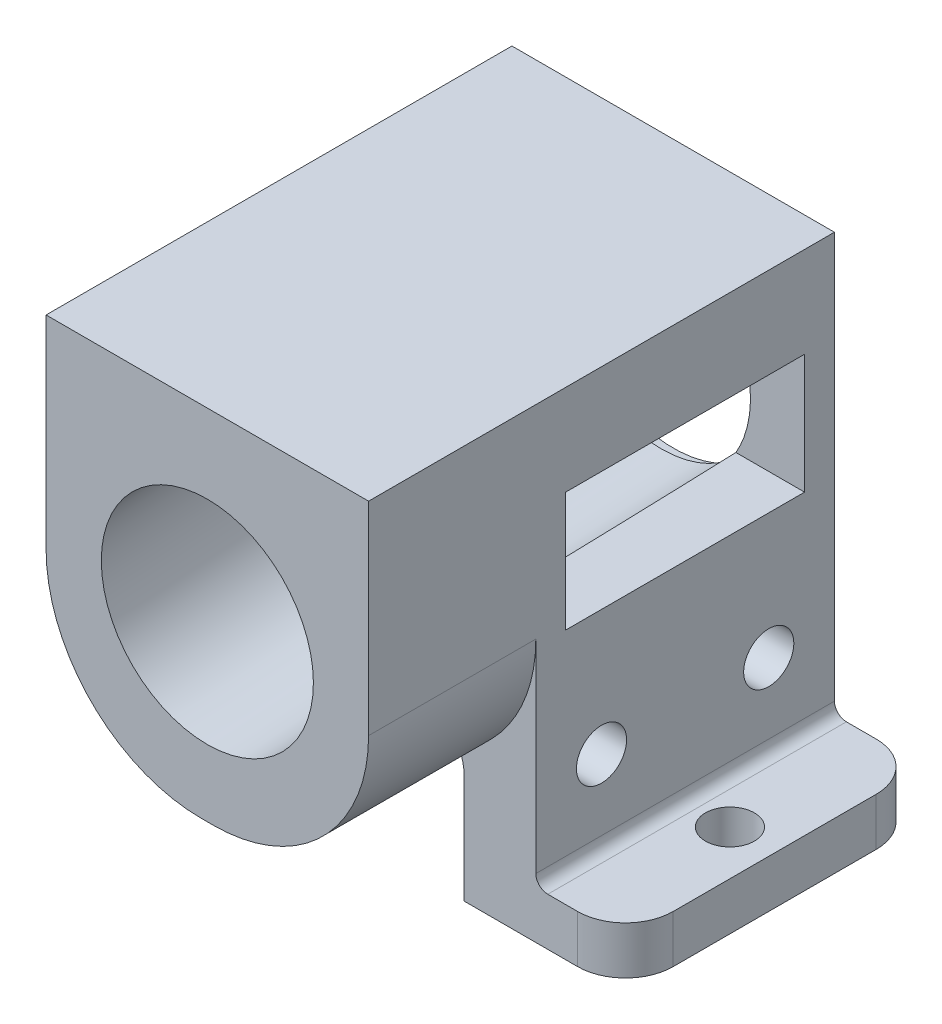
SolidWorks part; units mm, degrees
material "聚脂树脂"
ref_plane "前视基准面" through (0, 0, 0) normal (0, 0, 1) x (1, 0, 0)
ref_plane "上视基准面" through (0, 0, 0) normal (0, 1, 0) x (1, 0, 0)
ref_plane "右视基准面" through (0, 0, 0) normal (1, 0, 0) x (0, 0, -1)
sketch "草图1" plane through (0, 0, 0) normal (0, 0, 1) x (1, 0, 0)
  line L0 (0, 0) -> (0, 26.1)
  line L1 (-13.5, 39.6) -> (-13.5, 0)
  line L2 (-13.5, 39.6) -> (13.5, 39.6)
  line L3 (-13.5, 0) -> (13.5, 0)
  line L4 (13.5, 39.6) -> (13.5, 0)
  line L5 (-13.5, 39.6) -> (13.5, 0) construction
  line L6 (-13.5, 0) -> (13.5, 39.6) construction
  line L7 (13.5, 4) -> (-13.5, 4) construction
  line L8 (0, 4) -> (0, 0) construction
  line L9 (-13.5, 13.2062) -> (13.5, 13.2062)
  line L10 (-21, 4) -> (21, 4)
  line L11 (-21, 4) -> (-21, 0)
  line L12 (-21, 0) -> (21, 0)
  line L13 (21, 4) -> (21, 0)
  line L14 (-21, 4) -> (21, 0) construction
  line L15 (-21, 0) -> (21, 4) construction
  line L16 (-4, 13.2062) -> (4, 13.2062)
  line L17 (-4, 13.2062) -> (-4, 0)
  line L18 (-4, 0) -> (4, 0)
  line L19 (4, 13.2062) -> (4, 0)
  line L20 (-4, 13.2062) -> (4, 0) construction
  line L21 (-4, 0) -> (4, 13.2062) construction
  circle A0 centre (0, 26.1) radius 9
  circle A1 centre (0, 26.1) radius 13.5
  point P5 (0, 39.6)
  point P6 (0, 19.8)
  point P10 (0, 2)
  point P19 (0, 6.6031)
  point P26 (-4, 13.2062)
  dimension "D2" = 18
  dimension "D3" = 27
  dimension "D1" = 26.1
  dimension "D4" = 13.5
  dimension "D5" = 27
  dimension "D6" = 4
  dimension "0" = 0
  dimension "D7" = 4
  dimension "D8" = 42
  dimension "D9" = 8
  dimension "D10" = 13.5
extrude "凸台-拉伸3" add sketch "草图1" along normal blind 25 contours L0 A1 L9 | L9 A1 L0 | A1 L0 L10 L19 | A1 L17 L10 L0 | A1 L9 L4 | A1 L4 L2 | A1 L9 A0 | A1 L2 L1 | A1 L1 L9 | L11 L12 L1 L10 | L17 L10 L1 L3 | L19 L10 L0 L3 | L10 L17 L12 L0 | L13 L10 L4 L12 | L10 L19 L12 L4 region at (-2, 2, 0) region at (2, 2, 0) region at (-2.0229, 8.402, 0) region at (2.0229, 8.402, 0) region at (-8.75, 2, 0) region at (8.75, 2, 0) region at (-1.5046, 12.9632, 0) region at (1.5046, 12.9632, 0) region at (-17.25, 2, 0) region at (17.25, 2, 0) region at (-2, 13.5838, 0) region at (-10.9754, 16.1651, 0) region at (10.9754, 16.1651, 0) region at (-10.4845, 36.5845, 0) region at (10.4845, 36.5845, 0)
sketch "草图2" plane through (13.5, 0, 0) normal (1, 0, 0) x (0, 0, -1)
  line L0 (-12.5, 39.6) -> (-12.5, 13.2062) construction
  line L1 (-25, 39.6) -> (0, 39.6) construction
  line L2 (-25, 13.2062) -> (0, 13.2062) construction
  line L4 (-22.5, 21.4031) -> (-2.5, 21.4031)
  line L5 (-22.5, 21.4031) -> (-22.5, 31.4031)
  line L6 (-22.5, 31.4031) -> (-2.5, 31.4031)
  line L7 (-2.5, 21.4031) -> (-2.5, 31.4031)
  line L8 (-22.5, 21.4031) -> (-2.5, 31.4031) construction
  line L9 (-22.5, 31.4031) -> (-2.5, 21.4031) construction
  point P6 (-12.5, 26.4031)
  dimension "D1" = 10
  dimension "D2" = 20
extrude "切除-拉伸1" cut sketch "草图2" against normal through all
extrude "凸台-拉伸4" add sketch "草图1<8>" along normal blind 25 contours L17 L9 L1 L10 | L9 L19 L10 L4 region at (-8.75, 8.6031, 0) region at (8.75, 8.6031, 0)
sketch "草图1<8>" plane through (0, 0, 0) normal (0, 0, 1) x (1, 0, 0) same geometry as "草图1"
sketch "草图4" plane through (0, 4, 0) normal (0, 1, 0) x (1, 0, 0)
  line L0 (-17.25, 0) -> (-17.25, -25) construction
  line L1 (-21, 0) -> (-13.5, 0) construction
  line L2 (-21, -25) -> (-13.5, -25) construction
  circle A0 centre (-17.25, -12.5) radius 2.05
  dimension "D1" = 4.1
extrude "切除-拉伸2" cut sketch "草图4" against normal blind 25
mirror "镜向1" about plane through (0, 0, 0) normal (1, 0, 0) of "切除-拉伸2"
fillet "圆角5" radius 4 4 edges at (-21, 2, 25) (-21, 2, 0) (21, 2, 0) (21, 2, 25)
fillet "圆角7" radius 1 2 edges at (13.5, 4, 12.5) (-13.5, 4, 12.5)
sketch "草图6" plane through (0, 39.6, 0) normal (0, 1, 0) x (1, 0, 0)
  line L0 (-13.5, 0) -> (-13.5, -25)
  line L1 (-13.5, -25) -> (13.5, -25)
  line L2 (13.5, -25) -> (13.5, 0)
  line L3 (13.5, 0) -> (-13.5, 0)
extrude "切除-拉伸4" cut sketch "草图6" against normal blind 0.6
sketch "草图7" plane through (13.5, 0, 0) normal (1, 0, 0) x (0, 0, -1)
  circle A0 centre (-5.5, 10.9031) radius 2
  circle A1 centre (-19.5, 10.9031) radius 2
extrude "切除-拉伸5" cut sketch "草图7" against normal through all
sketch "草图8" plane through (0, 0, 25) normal (0, 0, 1) x (1, 0, 0)
  line L0 (0, 17.1) -> (0, 13.1)
  line L1 (0, 13.1) -> (0, 0) construction
  line L2 (-17, 0) -> (17, 0) construction
  line L3 (-13.5, 39) -> (-13.5, 5) construction
  line L4 (-7.5, -0.001) -> (7.5, -0.001)
  line L5 (-7.5, -0.001) -> (-7.5, 13.101)
  line L6 (-7.5, 13.101) -> (7.5, 13.101)
  line L7 (7.5, -0.001) -> (7.5, 13.101)
  line L8 (-7.5, -0.001) -> (7.5, 13.101) construction
  line L9 (-7.5, 13.101) -> (7.5, -0.001) construction
  circle A0 centre (0, 26.1) radius 9 construction
  point P6 (0, 6.55)
  line M12 (-17, 0) -> (17, 0)
  dimension "D1" = 4
  dimension "D2" = 6
extrude "切除-拉伸6" cut sketch "草图8" against normal through all contours L7 L6 L5 M12 region at (0, 6.5505, 25)
fillet "圆角10" radius 4 2 edges at (7.5, 13.101, 12.5) (-7.5, 13.101, 12.5)
sketch "草图10" plane through (0, 0, 0) normal (0, 0, -1) x (-1, 0, 0)
  circle A0 centre (0, 26.1) radius 9.5
  dimension "D1" = 19
extrude "切除-拉伸8" cut sketch "草图10" against normal blind 1
sketch "Sketch1" plane through (13.5, 0, 0) normal (1, 0, 0) x (0, 0, -1)
  circle A0 centre (-19.5, 10.9031) radius 2.1
  circle A1 centre (-5.5, 10.9031) radius 2.1
  dimension "D1" = 4.2
  dimension "D2" = 4.2
extrude "Cut-Extrude1" cut sketch "Sketch1" against normal through all both and the other way through all
sketch "Sketch2" plane through (0, 0, 25) normal (0, 0, 1) x (1, 0, 0)
  line L0 (13.5, 39) -> (13.5, 5) construction
  line L1 (-13.5, 39) -> (13.5, 39) construction
  line L2 (7.5, 0) -> (17, 0) construction
  circle A0 centre (9.5, 36) radius 2.5
  circle A1 centre (9.5, 17) radius 2.5
  dimension "D1" = 4
  dimension "D2" = 3
  dimension "D3" = 5
  dimension "D4" = 5
  dimension "D5" = 4
  dimension "D6" = 17
extrude "Cut-Extrude2" cut sketch "Sketch2" against normal through all both and the other way through all
mirror "Mirror1" about plane through (0, 0, 0) normal (1, 0, 0) of "Cut-Extrude2"
sketch "Sketch3" plane through (0, 0, 25) normal (0, 0, 1) x (1, 0, 0)
  line L0 (13.5, 39) -> (13.5, 5) construction
  line L1 (-13.5, 39) -> (13.5, 39)
  line L2 (-13.5, 39) -> (-13.5, 9)
  line L3 (-13.5, 9) -> (13.5, 9)
  line L4 (13.5, 39) -> (13.5, 9)
  dimension "D1" = 30
extrude "Boss-Extrude1" add sketch "Sketch3" along normal blind 14
sketch "Sketch4" plane through (0, 0, 0) normal (1, 0, 0) x (0, 0, -1)
  line L0 (0, 26.1) -> (-39, 23.5)
  line L1 (0, 39) -> (0, 5) construction
  line L2 (-39, 9) -> (-39, 39) construction
  line L3 (-39, 39) -> (0, 39) construction
  line L4 (0, 26.1) -> (0, 35.1)
  line L5 (0, 35.1) -> (-39, 32.4)
  line L7 (-39, 32.4) -> (-47.2336, 31.83)
  line L8 (-47.2336, 31.83) -> (-39, 23.5)
  dimension "D1" = 12.9
  dimension "D2" = 2.6
  dimension "D3" = 9
  dimension "D4" = 8.9
sketch "Sketch5" plane through (0, 0, 1) normal (0, 0, -1) x (-1, 0, 0)
  circle A0 centre (0, 26.1) radius 9
extrude "Boss-Extrude2" add sketch "Sketch5" against normal up to surface (24 mm away) up to face at (-7, 36, 25)
revolve "Cut-Revolve1" cut sketch "Sketch4" angle 360 about L0
extrude "Cut-Extrude3" cut sketch "草图2<2>" against normal through all both and the other way through all
sketch "草图2<2>" plane through (13.5, 0, 0) normal (1, 0, 0) x (0, 0, -1) same geometry as "草图2"
fillet "Fillet1" radius 13 2 edges at (13.5, 9, 32) (-13.5, 9, 32)
